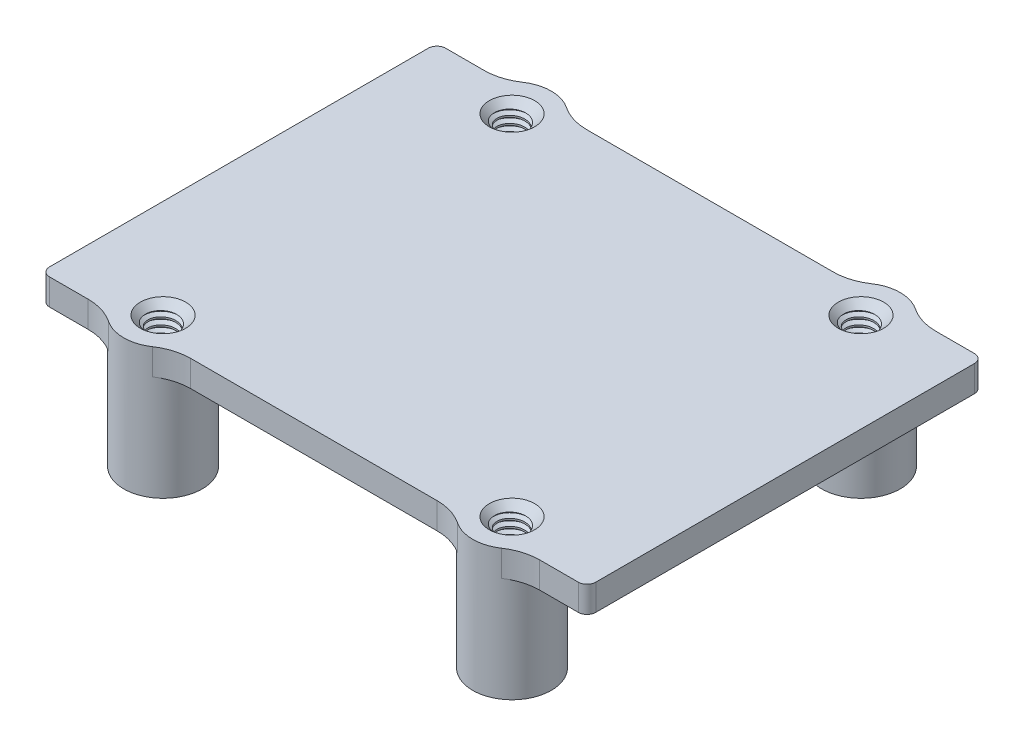
SolidWorks part; units mm, degrees
ref_plane "Front Plane" through (0, 0, 0) normal (0, 0, 1) x (1, 0, 0)
ref_plane "Top Plane" through (0, 0, 0) normal (0, 1, 0) x (1, 0, 0)
ref_plane "Right Plane" through (0, 0, 0) normal (1, 0, 0) x (0, 0, -1)
sketch "Sketch1" plane through (0, 0, 0) normal (0, 1, 0) x (1, 0, 0)
  line L1 (10, 10) -> (-10, 10)
  line L2 (10, 10) -> (10, -10)
  line L3 (10, -10) -> (-10, -10)
  line L4 (-10, 10) -> (-10, -10)
  line L5 (10, 10) -> (-10, -10) construction
  line L6 (10, -10) -> (-10, 10) construction
  line L7 (-15.65, 11.35) -> (15.65, 11.35)
  line L8 (-15.65, 11.35) -> (-15.65, -11.35)
  line L9 (-15.65, -11.35) -> (15.65, -11.35)
  line L10 (15.65, 11.35) -> (15.65, -11.35)
  line L11 (-15.65, 11.35) -> (15.65, -11.35) construction
  line L12 (-15.65, -11.35) -> (15.65, 11.35) construction
  circle A0 centre (-10, 10) radius 0.8
  circle A1 centre (10, 10) radius 0.8
  circle A2 centre (10, -10) radius 0.8
  circle A3 centre (-10, -10) radius 0.8
  circle A4 centre (-10, 10) radius 2.25
  circle A5 centre (10, 10) radius 2.25
  circle A6 centre (10, -10) radius 2.25
  circle A7 centre (-10, -10) radius 2.25
  point P0 (0, 0)
  point P10 (0, 0)
  dimension "D2" = 1.6
  dimension "D5" = 4.5
  dimension "D1" = 20
  dimension "D3" = 31.3
  dimension "D4" = 22.7
extrude "Boss-Extrude1" add sketch "Sketch1" along normal blind 1.5 contours A7 L4 A4 L7 L8 L9 | A7 L3 A6 L2 A5 L1 A4 L4 | A6 L9 L10 L7 A5 L2 | A7 L9 A6 L3 | A5 L7 A4 L1 | L2 A6 L3 A2 | L9 A6 L2 A2 L3 | L9 A6 | L9 A7 L3 A3 L4 | L3 A7 L4 A3 | L9 A7 | L2 A5 L7 L1 A1 | L1 A5 L2 A1 | L7 A5 | L7 A4 | L1 A4 L7 L4 A0 | L4 A4 L1 A0 region at (-8.956, 0, -8.956) region at (0, 0, -10.6813) region at (-8.475, 0, -10.0576) region at (0, 0, 0) region at (7.9201, 0, -10.6933) region at (8.956, 0, -8.956) region at (-10, 0, -11.717) region at (-13.0425, 0, 0) region at (10, 0, -11.717) region at (13.0425, 0, 0) region at (-8.956, 0, 8.956) region at (-10.0576, 0, 8.475) region at (11.5502, 0, 8.4498) region at (8.956, 0, 8.956) region at (0, 0, 10.6813) region at (-10, 0, 11.717) region at (10, 0, 11.717)
sketch "Sketch2" plane through (0, 0, 0) normal (0, -1, 0) x (1, 0, 0)
  circle A0 centre (-10, 10) radius 2.25
  arc A1 (-8.2, 11.35) -> (-11.8, 11.35) centre (-10, 10) ccw construction
  circle A2 centre (-10, 10) radius 0.8 construction
  circle A3 centre (-10, 10) radius 0.8
  circle A4 centre (-10, -10) radius 0.8 construction
  circle A5 centre (10, -10) radius 0.8 construction
  circle A6 centre (10, 10) radius 0.8 construction
  circle A7 centre (-10, -10) radius 0.8
  circle A8 centre (10, -10) radius 0.8
  circle A9 centre (10, 10) radius 0.8
  circle A10 centre (10, 10) radius 2.25
  circle A11 centre (10, -10) radius 2.25
  circle A12 centre (-10, -10) radius 2.25
extrude "Boss-Extrude2" add sketch "Sketch2" along normal blind 6
fillet "Fillet1" radius 0.5 4 edges at (-15.65, 0.75, -11.35) (-15.65, 0.75, 11.35) (15.65, 0.75, -11.35) (15.65, 0.75, 11.35)
fillet "Fillet2" radius 3 8 edges at (11.8, 0.75, 11.35) (8.2, 0.75, 11.35) (-8.2, 0.75, 11.35) (-11.8, 0.75, 11.35) (-11.8, 0.75, -11.35) (-8.2, 0.75, -11.35) (8.2, 0.75, -11.35) (11.8, 0.75, -11.35)
chamfer "Chamfer1" distance 0.5 angle 45 8 edges at (-10, 1.5, -9.2) (-10, 1.5, 10.8) (10, 1.5, 10.8) (10, 1.5, -9.2) (10, -6, -10.8) (10, -6, 9.2) (-10, -6, 9.2) (-10, -6, -10.8)
thread "Thread1" pitch 0.4 method cut profile "Thread Profile1" start angle 0, offset 1, length 0, pitch 0.4, diameter 1.6
ref_plane "Plane1" through (9.2, 2, -10) normal (0, 0, 1) x (-1, 0, 0)
sketch "Thread Profile1" plane through (9.2, 2, -10) normal (0, 0, 1) x (-1, 0, 0)
  line L0 (0, 0) -> (0, 0.4) construction
  line L1 (0, 0) -> (0.2165, 0.125)
  line L2 (0.2165, 0.125) -> (0.2165, 0.175)
  line L3 (0.2165, 0.175) -> (0, 0.3)
  line L4 (0.2165, 0.15) -> (0, 0.15) construction
  line L11 (0, 0) -> (0, 0.3)
  point P2 (0, 0)
  dimension "Pitch" = 0.4
  dimension "Profile_Angle" = 60
  dimension "Profile_Land" = 0.05
  dimension "Profile_Height" = 0.2165
thread "Thread2" pitch 0.4 method cut profile "Thread Profile2" start angle 0, offset 1, length 0, pitch 0.4, diameter 1.6
ref_plane "Plane2" through (9.2, 2, 10) normal (0, 0, 1) x (-1, 0, 0)
sketch "Thread Profile2" plane through (9.2, 2, 10) normal (0, 0, 1) x (-1, 0, 0)
  line L0 (0, 0) -> (0, 0.4) construction
  line L1 (0, 0) -> (0.2165, 0.125)
  line L2 (0.2165, 0.125) -> (0.2165, 0.175)
  line L3 (0.2165, 0.175) -> (0, 0.3)
  line L4 (0.2165, 0.15) -> (0, 0.15) construction
  line L11 (0, 0) -> (0, 0.3)
  point P2 (0, 0)
  dimension "Pitch" = 0.4
  dimension "Profile_Angle" = 60
  dimension "Profile_Land" = 0.05
  dimension "Profile_Height" = 0.2165
thread "Thread3" pitch 0.4 method cut profile "Thread Profile3" start angle 0, offset 1, length 0, pitch 0.4, diameter 1.6
ref_plane "Plane3" through (-10.8, 2, 10) normal (0, 0, 1) x (-1, 0, 0)
sketch "Thread Profile3" plane through (-10.8, 2, 10) normal (0, 0, 1) x (-1, 0, 0)
  line L0 (0, 0) -> (0, 0.4) construction
  line L1 (0, 0) -> (0.2165, 0.125)
  line L2 (0.2165, 0.125) -> (0.2165, 0.175)
  line L3 (0.2165, 0.175) -> (0, 0.3)
  line L4 (0.2165, 0.15) -> (0, 0.15) construction
  line L11 (0, 0) -> (0, 0.3)
  point P2 (0, 0)
  dimension "Pitch" = 0.4
  dimension "Profile_Angle" = 60
  dimension "Profile_Land" = 0.05
  dimension "Profile_Height" = 0.2165
thread "Thread4" pitch 0.4 method cut profile "Thread Profile4" start angle 0, offset 1, length 0, pitch 0.4, diameter 1.6
ref_plane "Plane4" through (-10.8, 2, -10) normal (0, 0, 1) x (-1, 0, 0)
sketch "Thread Profile4" plane through (-10.8, 2, -10) normal (0, 0, 1) x (-1, 0, 0)
  line L0 (0, 0) -> (0, 0.4) construction
  line L1 (0, 0) -> (0.2165, 0.125)
  line L2 (0.2165, 0.125) -> (0.2165, 0.175)
  line L3 (0.2165, 0.175) -> (0, 0.3)
  line L4 (0.2165, 0.15) -> (0, 0.15) construction
  line L11 (0, 0) -> (0, 0.3)
  point P2 (0, 0)
  dimension "Pitch" = 0.4
  dimension "Profile_Angle" = 60
  dimension "Profile_Land" = 0.05
  dimension "Profile_Height" = 0.2165
